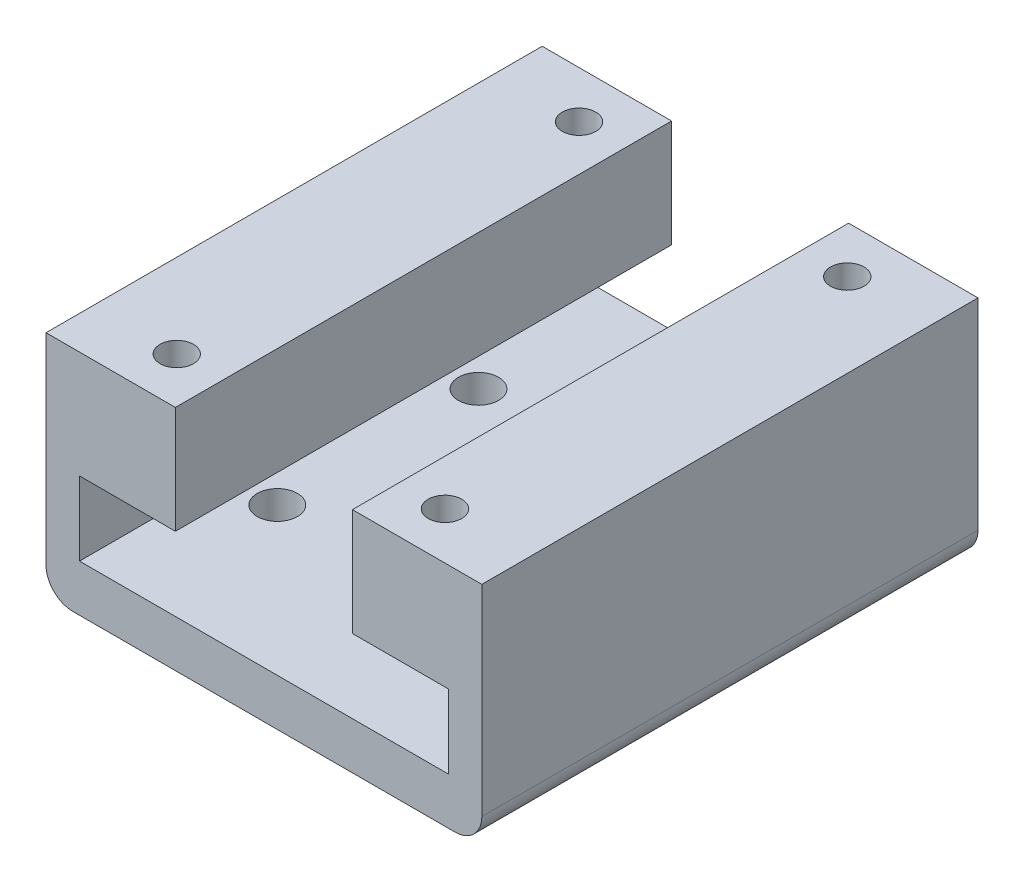
SolidWorks part; units mm, degrees
ref_plane "前视基准面" through (0, 0, 0) normal (0, 0, 1) x (1, 0, 0)
ref_plane "上视基准面" through (0, 0, 0) normal (0, 1, 0) x (1, 0, 0)
ref_plane "右视基准面" through (0, 0, 0) normal (1, 0, 0) x (0, 0, -1)
sketch "草图1" plane through (0, 0, 0) normal (0, 1, 0) x (1, 0, 0)
  line L1 (16.25, -18.5) -> (-16.25, -18.5)
  line L2 (16.25, -18.5) -> (16.25, 18.5)
  line L3 (16.25, 18.5) -> (-16.25, 18.5)
  line L4 (-16.25, -18.5) -> (-16.25, 18.5)
  line L5 (16.25, -18.5) -> (-16.25, 18.5) construction
  line L6 (16.25, 18.5) -> (-16.25, -18.5) construction
  point P0 (0, 0)
  dimension "D1" = 32.5
  dimension "D2" = 37
extrude "凸台-拉伸1" add sketch "草图1" along normal blind 17
sketch "草图2" plane through (0, 0, -18.5) normal (0, 0, -1) x (-1, 0, 0)
  line L0 (-16.25, 17) -> (16.25, 17) construction
  line L1 (-6.6, 9) -> (6.6, 9)
  line L2 (-6.6, 9) -> (-6.6, 17)
  line L3 (-6.6, 17) -> (6.6, 17)
  line L4 (6.6, 9) -> (6.6, 17)
  line L5 (-6.6, 9) -> (6.6, 17) construction
  line L6 (-6.6, 17) -> (6.6, 9) construction
  line L8 (-13.75, 3.5) -> (13.75, 3.5)
  line L9 (-13.75, 3.5) -> (-13.75, 9)
  line L10 (-13.75, 9) -> (13.75, 9)
  line L11 (13.75, 3.5) -> (13.75, 9)
  line L12 (-13.75, 3.5) -> (13.75, 9) construction
  line L13 (-13.75, 9) -> (13.75, 3.5) construction
  point P0 (0, 13)
  point P7 (0, 0)
  point P9 (0, 6.25)
  line M7 (16.25, 17) -> (-16.25, 17)
  dimension "D1" = 8
  dimension "D2" = 13.2
  dimension "D3" = 27.5
  dimension "D4" = 13.5
  dimension "D5" = 0
extrude "切除-拉伸2" cut sketch "草图2" against normal blind 45 contours L1 L4 L2 M7 | L8 L11 L10 L1 L9 region at (0, 13, -18.5) region at (0, 6.25, -18.5)
sketch "草图4" plane through (0, 0, 0) normal (0, -1, 0) x (1, 0, 0)
  line L1 (-10, -7.5) -> (10, -7.5) construction
  line L2 (-10, -7.5) -> (-10, 7.5) construction
  line L3 (-10, 7.5) -> (10, 7.5) construction
  line L4 (10, -7.5) -> (10, 7.5) construction
  line L5 (-10, -7.5) -> (10, 7.5) construction
  line L6 (-10, 7.5) -> (10, -7.5) construction
  circle A0 centre (-10, 7.5) radius 1.5
  circle A1 centre (10, 7.5) radius 1.5
  circle A2 centre (10, -7.5) radius 1.5
  circle A3 centre (-10, -7.5) radius 1.5
  point P0 (0, 0)
  dimension "D3" = 3
  dimension "D4" = 3
  dimension "D5" = 3
  dimension "D6" = 3
  dimension "D1" = 20
  dimension "D2" = 15
extrude "切除-拉伸3" cut sketch "草图4" against normal up to next
sketch "草图5" plane through (0, 17, 0) normal (0, 1, 0) x (1, 0, 0)
  line L1 (-10, -15) -> (10, -15) construction
  line L2 (-10, -15) -> (-10, 15) construction
  line L3 (-10, 15) -> (10, 15) construction
  line L4 (10, -15) -> (10, 15) construction
  line L5 (-10, -15) -> (10, 15) construction
  line L6 (-10, 15) -> (10, -15) construction
  circle A0 centre (-10, 15) radius 1.25
  circle A1 centre (10, 15) radius 1.25
  circle A2 centre (10, -15) radius 1.25
  circle A3 centre (-10, -15) radius 1.25
  point P0 (0, 0)
  point P11 (0, 0)
  dimension "D3" = 2.5
  dimension "D4" = 2.5
  dimension "D5" = 2.5
  dimension "D6" = 2.5
  dimension "D1" = 30
  dimension "D2" = 20
extrude "切除-拉伸4" cut sketch "草图5" against normal blind 2
fillet "圆角1" radius 2 2 edges at (16.25, 0, 0) (-16.25, 0, 0)
equation "\"33.5.00mm\"=34"
